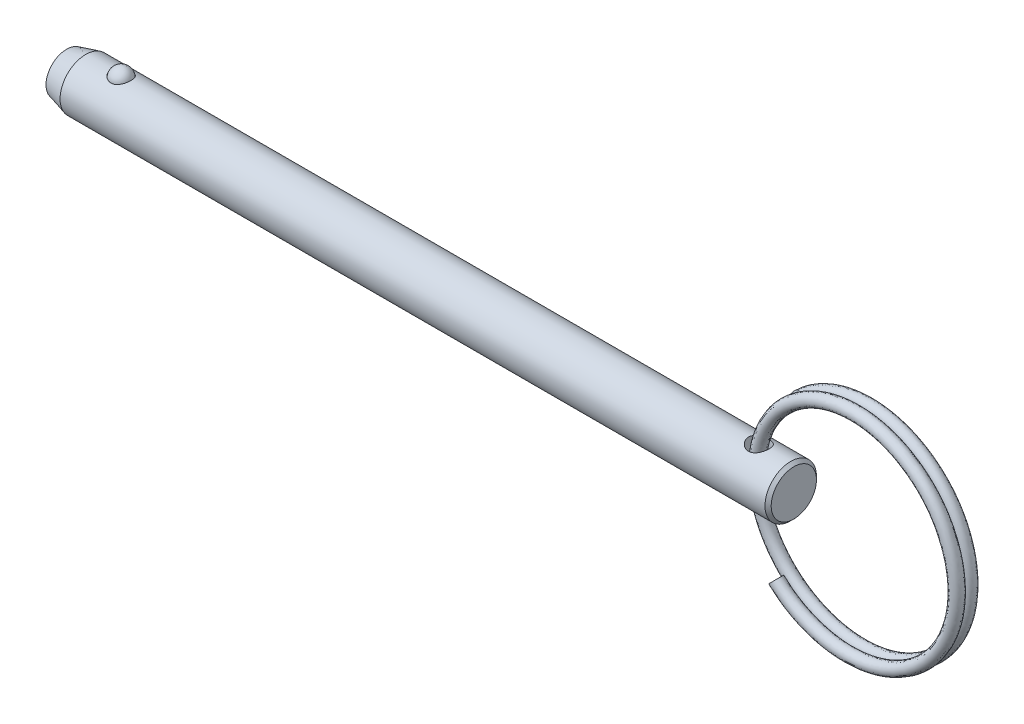
SolidWorks part; units mm, degrees
material "Plain Carbon Steel"
ref_plane "Front" through (0, 0, 0) normal (0, 0, 1) x (1, 0, 0)
ref_plane "Top" through (0, 0, 0) normal (0, 1, 0) x (1, 0, 0)
ref_plane "Right" through (0, 0, 0) normal (1, 0, 0) x (0, 0, -1)
sketch "Sketch1" plane through (0, 0, 0) normal (0, 0, 1) x (1, 0, 0)
  line L0 (44.8564, 2.794) -> (44.4754, 3.175)
  line L1 (44.4754, 3.175) -> (44.8564, 3.175) construction
  line L4 (44.8564, 2.794) -> (44.8564, 0)
  line L5 (44.8564, 3.175) -> (44.8564, 2.794) construction
  line L16 (44.4754, 3.175) -> (-42.4865, 3.175)
  line L17 (-44.8564, 3.175) -> (-44.8564, 2.54) construction
  line L19 (-42.4865, 3.175) -> (-44.8564, 3.175) construction
  line L22 (-44.8564, -3.175) -> (-42.4865, -3.175) construction
  line L23 (-38.1219, 2.8575) -> (-38.1219, -2.8575) construction
  line L24 (-44.8564, 0) -> (44.8564, 0)
  line L27 (44.8564, 0) -> (47.6504, 0) construction
  line L29 (-44.8564, 0) -> (-44.8564, -2.54) construction
  line L36 (39.2684, 0) -> (39.2684, 3.175) construction
  line L37 (-44.8564, 2.54) -> (-44.8564, 0)
  line L38 (-42.4865, -3.175) -> (44.8564, -3.175) construction
  line L39 (-44.8564, -2.54) -> (-44.8564, -3.175) construction
  line L40 (-42.4865, 3.175) -> (-44.8564, 2.54)
  line L42 (-42.4865, -3.175) -> (-44.8564, -2.54) construction
  line L43 (-42.4865, 3.175) -> (-42.4865, -3.175) construction
  circle A2 centre (-38.1219, 2.8575) radius 1.2319 construction
  point P35 (-36.9316, 3.175)
  dimension "A1" = 15
revolve "Revolve1" add sketch "Sketch1" angle 360 about L27
sketch "Sketch2" plane through (0, 0, 0) normal (0, 0, 1) x (1, 0, 0)
  line L0 (-36.8646, 2.8575) -> (-39.3792, 2.8575)
  line L1 (-38.1219, 4.0894) -> (-38.1219, 4.1148) construction
  line L2 (-36.8646, 2.8575) -> (-34.35, 2.8575) construction
  circle A0 centre (-38.1219, 2.8575) radius 1.2319 construction
  circle A1 centre (-38.1219, 2.8575) radius 1.2319 construction
  arc A2 (-39.3792, 2.8575) -> (-36.8646, 2.8575) centre (-38.1219, 2.8575) cw
  dimension "D1" = 0.0254
revolve "Cut-Revolve1" cut sketch "Sketch2" angle 360 about L2
sketch "Sketch3" plane through (0, 0, 0) normal (0, 0, 1) x (1, 0, 0)
  line L0 (-36.89, 2.8575) -> (-39.3538, 2.8575)
  line L1 (-36.89, 2.8575) -> (-34.4262, 2.8575) construction
  circle A0 centre (-38.1219, 2.8575) radius 1.2319 construction
  arc A1 (-36.89, 2.8575) -> (-39.3538, 2.8575) centre (-38.1219, 2.8575) ccw
revolve "Revolve2" add sketch "Sketch3" angle 360 about L1
sketch "Sketch4" plane through (0, 0, 0) normal (0, 0, 1) x (1, 0, 0)
  line L1 (40.5384, -3.175) -> (41.8084, -3.175)
  line L2 (40.5384, -3.175) -> (40.5384, 3.175)
  line L3 (40.5384, 3.175) -> (41.8084, 3.175)
  line L4 (41.8084, -3.175) -> (41.8084, 3.175)
  line L5 (40.5384, -3.175) -> (40.5384, -4.445) construction
  line L6 (41.8084, 3.175) -> (44.8564, 3.175) construction
  line L8 (39.2684, -3.175) -> (39.2684, 3.175) construction
  line L9 (39.2684, 0) -> (40.5384, 0) construction
  line L11 (40.5384, 0) -> (41.8084, 0) construction
  line L12 (44.4754, 3.175) -> (-42.4865, 3.175) construction
  line L14 (-42.4865, -3.175) -> (44.8564, -3.175) construction
  dimension "D1" = 2.54
revolve "Cut-Revolve2" cut sketch "Sketch4" angle 360 about L2
sketch "Sketch5" plane through (0, 0, 0) normal (0, 0, 1) x (1, 0, 0)
  line L0 (0, 0) -> (39.5614, 0) construction
  line L1 (39.5614, 0) -> (39.5614, 3.175) construction
  line L2 (44.4754, 3.175) -> (-42.4865, 3.175) construction
  line L3 (53.0234, 0) -> (66.4854, 0) construction
  line L4 (41.8084, 3.175) -> (41.5154, 3.175) construction
  line L5 (40.5384, 3.175) -> (41.8084, 3.175) construction
  line L6 (39.9412, 3.175) -> (39.9412, -3.175) construction
  line L7 (39.5614, 3.175) -> (39.2684, 3.175) construction
  line L8 (40.5384, -3.175) -> (41.8084, -3.175) construction
  line L9 (39.9412, -3.175) -> (41.8084, -3.175) construction
  line L10 (39.5614, 0) -> (53.0234, 0) construction
  line L12 (41.5154, 3.175) -> (39.9412, 3.175) construction
  line L13 (53.0234, 11.938) -> (53.0234, 13.462) construction
  circle A0 centre (53.0234, 0) radius 13.462
  circle A1 centre (53.0234, 0) radius 11.938 construction
  circle A2 centre (53.0234, 0) radius 12.7 construction
  point P26 (53.0234, 12.7)
curve "Helix/Spiral1" pitch 1.5494 height 1.3557 radius 13.462 left hand yes centre (53.0234, 0, 0) axis (0, 0, -1) start towards (1, 0, 0)
sketch "Sketch6" plane through (114.0038, 0, 0) normal (0, 1, 0) x (0, 0, -1)
  line L0 (0, 72.9184) -> (0, 73.6804) construction
  line L1 (0, 73.6804) -> (0, 74.4424) construction
  circle A0 centre (0, 73.6804) radius 0.762
  dimension "D1" = 1.524
sketch "Sketch7" plane through (0, 0, 0) normal (0, 0, 1) x (1, 0, 0)
  circle A0 centre (53.0234, 0) radius 13.462 construction
  circle A1 centre (53.0234, 0) radius 13.462
curve "Helix/Spiral2" pitch 1.5494 height 1.3557 radius 13.462 left hand yes centre (53.0234, 0, 0) axis (0, 0, 1) start towards (1, 0, 0)
sweep "Sweep1" add profiles "Sketch6" path "Helix/Spiral1"
sweep "Sweep2" add profiles "Sketch6<2>" path "Helix/Spiral2"
sketch "Sketch6<2>" plane through (114.0038, 0, 0) normal (0, 1, 0) x (0, 0, -1) same geometry as "Sketch6"
equation "\"D12@Sketch1\"=\"A@Sketch1\" * 0.80"
equation "\"D2@Sketch1\"=\"A@Sketch1\" * 0.9"
equation "\"D1@Sketch4\" = \"A@Sketch1\" / 2.5"
equation "\"Ring OD@Sketch5\" = \"R Ring Dia@Sketch5\" * 0.06"
equation "\"D4@Helix/Spiral1\"=\"Ring OD@Sketch5\" + 0.001"
equation "\"D1@Sketch6\"=\"Ring OD@Sketch5\""
equation "\"D4@Helix/Spiral2\" = \"D4@Helix/Spiral1\""
equation "\"D5@Helix/Spiral2\" = \"D5@Helix/Spiral1\""
